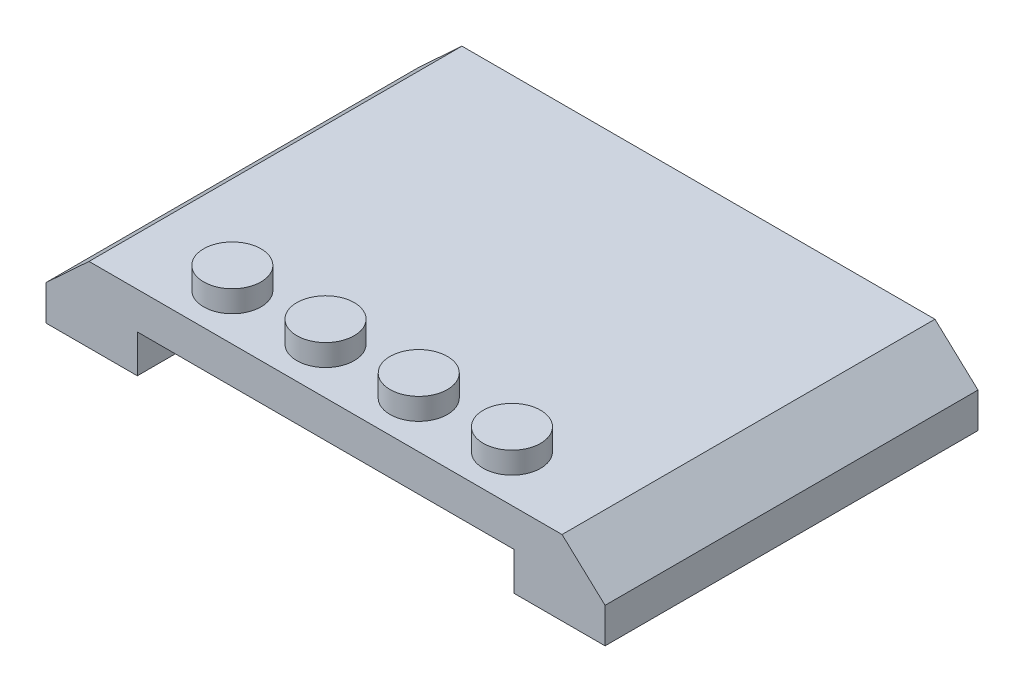
SolidWorks part; units mm, degrees
ref_plane "Front Plane" through (0, 0, 0) normal (0, 0, 1) x (1, 0, 0)
ref_plane "Top Plane" through (0, 0, 0) normal (0, 1, 0) x (1, 0, 0)
ref_plane "Right Plane" through (0, 0, 0) normal (1, 0, 0) x (0, 0, -1)
sketch "Sketch1" plane through (0, 0, 0) normal (0, 0, 1) x (1, 0, 0)
  line L4 (23.875, 0) -> (23.875, 3)
  line L5 (23.875, 3) -> (20.2, 6.4)
  line L6 (20.2, 6.4) -> (-20.2, 6.4)
  line L7 (-20.2, 6.4) -> (-23.875, 3)
  line L8 (-23.875, 3) -> (-23.875, 0)
  line L10 (-23.875, 0) -> (23.875, 0)
  point P0 (0, 0)
  point P12 (0, 6.4)
  dimension "D1" = 3
  dimension "D2" = 3
  dimension "D3" = 6.4
  dimension "D4" = 5.0066
  dimension "D5" = 5.0066
  dimension "D8" = 40.4
extrude "Boss-Extrude1" add sketch "Sketch1" against normal blind 31.85
sketch "Sketch2" plane through (0, 0, 0) normal (0, 0, 1) x (1, 0, 0)
  line L0 (-16.075, 0) -> (-16.075, 3.25)
  line L1 (-23.875, 0) -> (23.875, 0) construction
  line L2 (-16.075, 3.25) -> (16.075, 3.25)
  line L3 (16.075, 3.25) -> (16.075, 0)
  line L4 (23.875, 0) -> (23.875, 3) construction
  line L5 (-23.875, 3) -> (-23.875, 0) construction
  line L6 (20.2, 6.4) -> (-20.2, 6.4) construction
  dimension "D1" = 7.8
  dimension "D2" = 7.8
  dimension "D3" = 3.15
extrude "Cut-Extrude1" cut sketch "Sketch2" against normal blind 24.55 and the other way through all flip side to cut
shell "Shell1" thickness 1.6 removed face at (0, 0, -14.1)
ref_plane "Plane1" through (0, 0.2, 0) normal (0, -1, 0) x (-1, 0, 0)
sketch "Sketch3" plane through (0, 0.2, 0) normal (0, -1, 0) x (-1, 0, 0)
  line L5 (23.875, 31.85) -> (23.875, 0) construction
  line L6 (23.875, 0) -> (16.075, 0) construction
  line L7 (0, -7.1814) -> (0, 40.2887) construction
  circle A0 centre (19.975, 7.9625) radius 1.5
  circle A1 centre (19.975, 7.9625) radius 0.55
  circle A2 centre (19.975, 15.925) radius 1.5
  circle A3 centre (19.975, 15.925) radius 0.55
  circle A4 centre (19.975, 23.8875) radius 1.5
  circle A5 centre (19.975, 23.8875) radius 0.55
  circle A6 centre (-19.975, 23.8875) radius 0.55
  circle A7 centre (-19.975, 23.8875) radius 1.5
  circle A8 centre (-19.975, 15.925) radius 0.55
  circle A9 centre (-19.975, 15.925) radius 1.5
  circle A10 centre (-19.975, 7.9625) radius 0.55
  circle A11 centre (-19.975, 7.9625) radius 1.5
  dimension "D3" = 3
  dimension "D4" = 1.1
  dimension "D6" = 7.9625
  dimension "D1" = 3.9
  dimension "D2" = 7.9625
  dimension "D5" = 3
extrude "Boss-Extrude2" add sketch "Sketch3" against normal up to surface (4.6 mm away) up to face at (0, 4.8, -14.9)
sketch "Sketch4" plane through (0, 3.25, 0) normal (0, -1, 0) x (1, 0, 0)
  line L0 (16.075, 0) -> (-16.075, 0) construction
  line L1 (-16.075, -7.3) -> (16.075, -7.3)
  line L2 (-16.075, -7.3) -> (-16.075, -24.55)
  line L3 (-16.075, -24.55) -> (16.075, -24.55)
  line L4 (16.075, -7.3) -> (16.075, -24.55)
  line L5 (-16.075, -7.3) -> (16.075, -24.55) construction
  line L6 (-16.075, -24.55) -> (16.075, -7.3) construction
  point P0 (0, -15.925)
  dimension "D1" = 7.3
  dimension "D2" = 32.15
extrude "Cut-Extrude2" cut sketch "Sketch4" against normal blind 1.95
sketch "Sketch5" plane through (0, 3.25, 0) normal (0, -1, 0) x (1, 0, 0)
  line L0 (16.075, 0) -> (16.075, -7.3) construction
  line L1 (-16.075, -1.5) -> (16.075, -1.5)
  line L2 (-16.075, -1.5) -> (-16.075, -6.15)
  line L3 (-16.075, -6.15) -> (16.075, -6.15)
  line L4 (16.075, -1.5) -> (16.075, -6.15)
  line L5 (-16.075, -1.5) -> (16.075, -6.15) construction
  line L6 (-16.075, -6.15) -> (16.075, -1.5) construction
  line L7 (16.075, 0) -> (-16.075, 0) construction
  line L8 (16.075, -7.3) -> (-16.075, -7.3) construction
  point P0 (0, -3.825)
  dimension "D1" = 1.5
  dimension "D2" = 1.15
  dimension "D3" = 32.15
extrude "Cut-Extrude3" cut sketch "Sketch5" against normal blind 2.25
sketch "Sketch6" plane through (0, 6.4, 0) normal (0, 1, 0) x (1, 0, 0)
  line L0 (0, 34.7983) -> (0, -4.6524) construction
  line L1 (20.2, 0) -> (-20.2, 0) construction
  circle A0 centre (-3.98, 3.98) radius 2.45
  circle A1 centre (3.98, 3.98) radius 2.45
  circle A2 centre (-11.94, 3.98) radius 2.45
  circle A3 centre (11.94, 3.98) radius 2.45
  point P13 (0, 0)
  dimension "D2" = 7.96
  dimension "D3" = 4.9
  dimension "D4" = 4.9
  dimension "D5" = 7.96
  dimension "D6" = 4.9
  dimension "D7" = 7.96
  dimension "D8" = 4.9
  dimension "D1" = 3.98
  dimension "D9" = 3.98
extrude "Boss-Extrude3" add sketch "Sketch6" along normal blind 1.85
sketch "Sketch7" plane through (0, 5.5, 0) normal (0, -1, 0) x (1, 0, 0)
  circle A0 centre (-11.94, -3.98) radius 0.95
  circle A1 centre (-3.98, -3.98) radius 0.95
  circle A2 centre (3.98, -3.98) radius 0.95
  circle A3 centre (11.94, -3.98) radius 0.95
  dimension "D1" = 1.9
extrude "Cut-Extrude4" cut sketch "Sketch7" against normal blind 1.65
